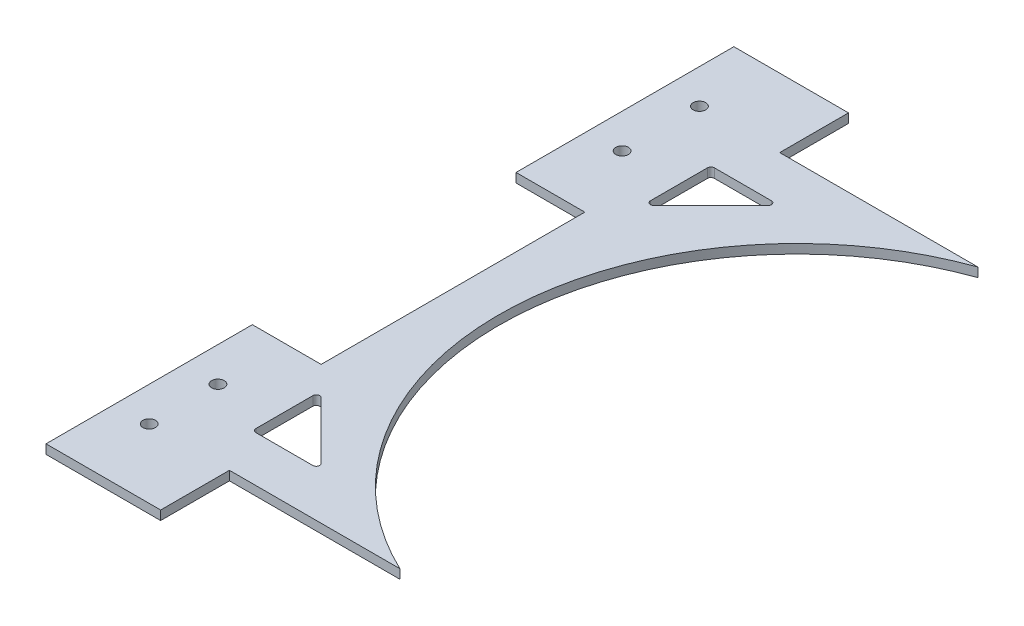
SolidWorks part; units mm, degrees
material "A-玻璃纤维"
ref_plane "前视基准面" through (0, 0, 0) normal (0, 0, 1) x (1, 0, 0)
ref_plane "上视基准面" through (0, 0, 0) normal (0, 1, 0) x (1, 0, 0)
ref_plane "右视基准面" through (0, 0, 0) normal (1, 0, 0) x (0, 0, -1)
other "Configuration Table"
sketch "草图1" plane through (0, 0, 0) normal (0, 1, 0) x (1, 0, 0)
  line L0 (0, 0) -> (360, 0)
  line L1 (360, 0) -> (360, -300)
  line L2 (360, -300) -> (0, -300)
  line L3 (0, -300) -> (0, 0)
  dimension "D1" = 360
  dimension "D2" = 300
extrude "凸台-拉伸1" add sketch "草图1" along normal blind 4
sketch "草图2" plane through (0, 4, 0) normal (0, 1, 0) x (1, 0, 0)
  line L0 (0, 0) -> (50, 0)
  line L1 (360, 0) -> (0, 0) construction
  line L2 (50, 0) -> (50, -30)
  line L3 (50, -30) -> (0, -30)
  line L4 (0, 0) -> (0, -300) construction
  line L5 (0, -30) -> (0, 0)
  line L6 (360, 0) -> (310, 0)
  line L7 (310, 0) -> (310, -30)
  line L8 (310, -30) -> (360, -30)
  line L9 (360, -300) -> (360, 0) construction
  line L10 (360, -30) -> (360, 0)
  line L11 (50, 0) -> (310, 0)
  line L12 (50, -30) -> (310, -30)
  line L13 (50, -30) -> (50, 0)
  line L14 (310, 0) -> (310, -30)
  line L15 (50, -30) -> (50, -300)
  line L16 (0, -300) -> (360, -300) construction
  line L17 (310, -30) -> (310, -297.4148)
  line L18 (310, -297.4148) -> (310, -308.1659)
  line L19 (0, -300) -> (0, -270)
  line L20 (0, -270) -> (360, -270)
  line M2 (0, -300) -> (360, -300)
  line M4 (360, 0) -> (0, 0)
extrude "切除-拉伸1" cut sketch "草图2" against normal through all contours L2 L12 L7 M4 | L20 L15 L18 L17 M2 region at (180, 4, 15) region at (180, 4, 285)
sketch "草图3" plane through (0, 4, 0) normal (0, 1, 0) x (1, 0, 0)
  line L0 (0, -300) -> (30, -300)
  line L1 (0, -300) -> (50, -300) construction
  line L2 (30, -300) -> (30, -210)
  line L3 (30, -210) -> (0, -210)
  line L4 (0, 0) -> (0, -300) construction
  line L5 (0, 0) -> (0, -95)
  line L6 (0, -95) -> (30, -95)
  line L7 (30, -95) -> (30, -210)
  line L8 (0, -210) -> (0, -95)
  line L9 (360, -300) -> (310, -300)
  line L10 (310, -300) -> (310, -30)
  line L11 (30, -95) -> (360, -95)
  line L12 (360, -300) -> (360, 0) construction
  line L13 (30, -210) -> (360, -210)
  line L14 (360, -300) -> (330, -300)
  line L15 (330, -300) -> (330, 0)
  line L16 (360, 0) -> (310, 0) construction
  line M4 (0, 0) -> (0, -300)
  line M6 (360, -300) -> (360, 0)
extrude "切除-拉伸2" cut sketch "草图3" against normal through all contours L7 L6 L3 M4 | L15 L13 L11 M6 region at (15, 4, 152.5) region at (345, 4, 152.5)
sketch "草图4" plane through (0, 4, 0) normal (0, 1, 0) x (1, 0, 0)
  line L0 (30, -152.5) -> (330, -152.5)
  line L1 (30, -95) -> (30, -210) construction
  line L2 (330, -210) -> (330, -95) construction
  line L3 (180, -30) -> (180, -270)
  line L4 (50, -30) -> (310, -30) construction
  line L5 (50, -270) -> (310, -270) construction
  circle A1 centre (180, -152.5) radius 130
  line M6 (50, -270) -> (310, -270)
  line M16 (310, -30) -> (50, -30)
extrude "切除-拉伸3" cut sketch "草图4" against normal through all contours A1 L0 L3 M16 | L0 A1 L3 M16 | L0 A1 L3 M6 | A1 L0 L3 M6 region at (124.1759, 4, 98.5055) region at (123.5768, 4, 205.2114) region at (235.8241, 4, 98.5055) region at (236.4232, 4, 205.2114) body kept at (0, 0, 0)
sketch "草图5" plane through (0, 4, 0) normal (0, 1, 0) x (1, 0, 0)
  line L0 (0, -300) -> (15, -300)
  line L1 (0, -300) -> (50, -300) construction
  line L2 (15, -300) -> (15, 0)
  line L3 (50, 0) -> (0, 0) construction
  line L4 (15, -300) -> (15, -270)
  line L5 (15, -270) -> (15, -240)
  line L6 (15, 0) -> (15, -30)
  line L7 (15, -30) -> (15, -63.744)
  circle A0 centre (15, -270) radius 2.75
  circle A1 centre (15, -240) radius 2.75
  circle A2 centre (15, -30) radius 2.75
  circle A3 centre (15, -63.744) radius 2.75
extrude "切除-拉伸4" cut sketch "草图5" against normal through all contours L7 A2 L2 | L2 A2 L7 | L2 A3 | L2 A3 | L2 A1 | L2 A1 | L4 A0 L2 | L2 A0 L4 region at (13.8329, 4, 270) region at (13.8329, 4, 30) region at (16.1671, 4, 30) region at (13.8329, 4, 63.744) region at (16.1671, 4, 63.744) region at (13.8329, 4, 240) region at (16.1671, 4, 240) region at (16.1671, 4, 270)
sketch "草图6" plane through (0, 4, 0) normal (0, 1, 0) x (1, 0, 0)
  line L0 (50, -30) -> (50, -50)
  line L1 (50, -50) -> (66.3787, -50)
  line L2 (67.4393, -52.5607) -> (42.5607, -77.4393)
  line L3 (40, -76.3787) -> (40, -51.5)
  line L4 (41.5, -50) -> (50, -50)
  line L6 (41.5, -50) -> (41.5, -51.5)
  line L9 (41.4934, -76.3718) -> (41.5, -76.3787)
  arc A0 (41.5, -50) -> (40, -51.5) centre (41.5, -51.5) ccw
  arc A1 (40, -76.3787) -> (42.5607, -77.4393) centre (41.5, -76.3787) ccw
  arc A2 (67.4393, -52.5607) -> (66.3787, -50) centre (66.3787, -51.5) ccw
extrude "切除-拉伸5" cut sketch "草图6" against normal through all contours L2 A2 L1 L4 A0 L3 A1 region at (49.9538, 4, 59.9538)
ref_plane "基准面1" through (0, 0, 150) normal (0, 0, 1) x (1, 0, 0)
mirror "镜向1" about plane through (0, 0, 150) normal (0, 0, 1) of "切除-拉伸5"
